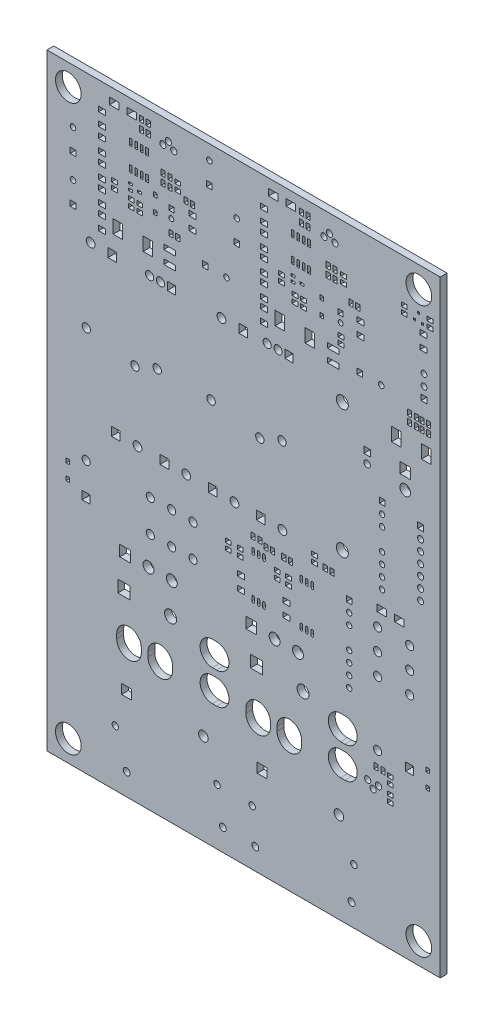
SolidWorks part; units mm, degrees
ref_plane "Plan de face" through (0, 0, 0) normal (0, 0, 1) x (1, 0, 0)
ref_plane "Plan de dessus" through (0, 0, 0) normal (0, 1, 0) x (1, 0, 0)
ref_plane "Plan de droite" through (0, 0, 0) normal (1, 0, 0) x (0, 0, -1)
sketch "Model" plane through (0, 0, 0) normal (0, 0, 1) x (1, 0, 0)
  line L0 (23.625, 30.9) -> (23.625, 31.9)
  line L1 (29.375, 31.9) -> (29.375, 30.9)
  line L2 (23.625, 30.9) -> (23.625, 31.9)
  line L3 (29.375, 31.9) -> (29.375, 30.9)
  line L4 (16.325, 30.9) -> (16.325, 31.9)
  line L5 (22.075, 31.9) -> (22.075, 30.9)
  line L6 (16.325, 30.9) -> (16.325, 31.9)
  line L7 (22.075, 31.9) -> (22.075, 30.9)
  line L8 (39.7, 36.225) -> (38.7, 36.225)
  line L9 (38.7, 41.975) -> (39.7, 41.975)
  line L10 (39.7, 36.225) -> (38.7, 36.225)
  line L11 (38.7, 41.975) -> (39.7, 41.975)
  line L12 (39.7, 28.925) -> (38.7, 28.925)
  line L13 (38.7, 34.675) -> (39.7, 34.675)
  line L14 (39.7, 28.925) -> (38.7, 28.925)
  line L15 (38.7, 34.675) -> (39.7, 34.675)
  line L16 (53.825, 30.9) -> (53.825, 31.9)
  line L17 (59.575, 31.9) -> (59.575, 30.9)
  line L18 (53.825, 30.9) -> (53.825, 31.9)
  line L19 (59.575, 31.9) -> (59.575, 30.9)
  line L20 (46.525, 30.9) -> (46.525, 31.9)
  line L21 (52.275, 31.9) -> (52.275, 30.9)
  line L22 (46.525, 30.9) -> (46.525, 31.9)
  line L23 (52.275, 31.9) -> (52.275, 30.9)
  line L24 (69.7, 36.225) -> (68.7, 36.225)
  line L25 (68.7, 41.975) -> (69.7, 41.975)
  line L26 (69.7, 36.225) -> (68.7, 36.225)
  line L27 (68.7, 41.975) -> (69.7, 41.975)
  line L28 (69.7, 28.925) -> (68.7, 28.925)
  line L29 (68.7, 34.675) -> (69.7, 34.675)
  line L30 (69.7, 28.925) -> (68.7, 28.925)
  line L31 (68.7, 34.675) -> (69.7, 34.675)
  line L32 (87.1159, 131.935) -> (86.6841, 131.935)
  line L33 (86.6841, 131.935) -> (86.6841, 132.443)
  line L34 (86.6841, 132.443) -> (87.1159, 132.443)
  line L35 (87.1159, 132.443) -> (87.1159, 131.935)
  line L36 (86.1761, 130.157) -> (85.7443, 130.157)
  line L37 (85.7443, 130.157) -> (85.7443, 130.665)
  line L38 (85.7443, 130.665) -> (86.1761, 130.665)
  line L39 (86.1761, 130.665) -> (86.1761, 130.157)
  line L40 (88.0811, 130.157) -> (87.6493, 130.157)
  line L41 (87.6493, 130.157) -> (87.6493, 130.665)
  line L42 (87.6493, 130.665) -> (88.0811, 130.665)
  line L43 (88.0811, 130.665) -> (88.0811, 130.157)
  line L44 (77.25, 66.825) -> (77.25, 68.375)
  line L45 (77.25, 68.375) -> (79.45, 68.375)
  line L46 (79.45, 68.375) -> (79.45, 66.825)
  line L47 (79.45, 66.825) -> (77.25, 66.825)
  line L48 (81.35, 66.825) -> (81.35, 68.375)
  line L49 (81.35, 68.375) -> (83.55, 68.375)
  line L50 (83.55, 68.375) -> (83.55, 66.825)
  line L51 (83.55, 66.825) -> (81.35, 66.825)
  line L52 (58.15, 139.875) -> (58.15, 138.325)
  line L53 (58.15, 138.325) -> (55.95, 138.325)
  line L54 (55.95, 138.325) -> (55.95, 139.875)
  line L55 (55.95, 139.875) -> (58.15, 139.875)
  line L56 (54.05, 139.875) -> (54.05, 138.325)
  line L57 (54.05, 138.325) -> (51.85, 138.325)
  line L58 (51.85, 138.325) -> (51.85, 139.875)
  line L59 (51.85, 139.875) -> (54.05, 139.875)
  line L60 (20.95, 139.775) -> (20.95, 138.225)
  line L61 (20.95, 138.225) -> (18.75, 138.225)
  line L62 (18.75, 138.225) -> (18.75, 139.775)
  line L63 (18.75, 139.775) -> (20.95, 139.775)
  line L64 (16.85, 139.775) -> (16.85, 138.225)
  line L65 (16.85, 138.225) -> (14.65, 138.225)
  line L66 (14.65, 138.225) -> (14.65, 139.775)
  line L67 (14.65, 139.775) -> (16.85, 139.775)
  line L68 (44.875, 109.125) -> (46.925, 109.125)
  line L69 (46.925, 109.125) -> (46.925, 107.075)
  line L70 (46.925, 107.075) -> (44.875, 107.075)
  line L71 (44.875, 107.075) -> (44.875, 109.125)
  line L72 (44.875, 109.125) -> (46.925, 109.125)
  line L73 (46.925, 109.125) -> (46.925, 107.075)
  line L74 (46.925, 107.075) -> (44.875, 107.075)
  line L75 (44.875, 107.075) -> (44.875, 109.125)
  line L76 (14.275, 109.125) -> (16.325, 109.125)
  line L77 (16.325, 109.125) -> (16.325, 107.075)
  line L78 (16.325, 107.075) -> (14.275, 107.075)
  line L79 (14.275, 107.075) -> (14.275, 109.125)
  line L80 (14.275, 109.125) -> (16.325, 109.125)
  line L81 (16.325, 109.125) -> (16.325, 107.075)
  line L82 (16.325, 107.075) -> (14.275, 107.075)
  line L83 (14.275, 107.075) -> (14.275, 109.125)
  line L84 (87.6, 106.075) -> (89.8, 106.075)
  line L85 (89.8, 106.075) -> (89.8, 102.925)
  line L86 (89.8, 102.925) -> (87.6, 102.925)
  line L87 (87.6, 102.925) -> (87.6, 106.075)
  line L88 (80.6, 106.075) -> (82.8, 106.075)
  line L89 (82.8, 106.075) -> (82.8, 102.925)
  line L90 (82.8, 102.925) -> (80.6, 102.925)
  line L91 (80.6, 102.925) -> (80.6, 106.075)
  line L92 (55.6, 112.825) -> (53.4, 112.825)
  line L93 (53.4, 112.825) -> (53.4, 115.975)
  line L94 (53.4, 115.975) -> (55.6, 115.975)
  line L95 (55.6, 115.975) -> (55.6, 112.825)
  line L96 (62.6, 112.825) -> (60.4, 112.825)
  line L97 (60.4, 112.825) -> (60.4, 115.975)
  line L98 (60.4, 115.975) -> (62.6, 115.975)
  line L99 (62.6, 115.975) -> (62.6, 112.825)
  line L100 (17.7, 112.425) -> (15.5, 112.425)
  line L101 (15.5, 112.425) -> (15.5, 115.575)
  line L102 (15.5, 115.575) -> (17.7, 115.575)
  line L103 (17.7, 115.575) -> (17.7, 112.425)
  line L104 (24.7, 112.425) -> (22.5, 112.425)
  line L105 (22.5, 112.425) -> (22.5, 115.575)
  line L106 (22.5, 115.575) -> (24.7, 115.575)
  line L107 (24.7, 115.575) -> (24.7, 112.425)
  line L108 (49.175, 20.075) -> (49.175, 22.325)
  line L109 (49.175, 22.325) -> (51.425, 22.325)
  line L110 (51.425, 22.325) -> (51.425, 20.075)
  line L111 (51.425, 20.075) -> (49.175, 20.075)
  line L112 (49.175, 20.075) -> (49.175, 22.325)
  line L113 (49.175, 22.325) -> (51.425, 22.325)
  line L114 (51.425, 22.325) -> (51.425, 20.075)
  line L115 (51.425, 20.075) -> (49.175, 20.075)
  line L116 (17.475, 20.175) -> (17.475, 22.425)
  line L117 (17.475, 22.425) -> (19.725, 22.425)
  line L118 (19.725, 22.425) -> (19.725, 20.175)
  line L119 (19.725, 20.175) -> (17.475, 20.175)
  line L120 (17.475, 20.175) -> (17.475, 22.425)
  line L121 (17.475, 22.425) -> (19.725, 22.425)
  line L122 (19.725, 22.425) -> (19.725, 20.175)
  line L123 (19.725, 20.175) -> (17.475, 20.175)
  line L124 (61.005, 134.275) -> (61.605, 134.275)
  line L125 (61.605, 134.275) -> (61.605, 132.725)
  line L126 (61.605, 132.725) -> (61.005, 132.725)
  line L127 (61.005, 132.725) -> (61.005, 134.275)
  line L128 (59.735, 134.275) -> (60.335, 134.275)
  line L129 (60.335, 134.275) -> (60.335, 132.725)
  line L130 (60.335, 132.725) -> (59.735, 132.725)
  line L131 (59.735, 132.725) -> (59.735, 134.275)
  line L132 (58.465, 134.275) -> (59.065, 134.275)
  line L133 (59.065, 134.275) -> (59.065, 132.725)
  line L134 (59.065, 132.725) -> (58.465, 132.725)
  line L135 (58.465, 132.725) -> (58.465, 134.275)
  line L136 (57.195, 134.275) -> (57.795, 134.275)
  line L137 (57.795, 134.275) -> (57.795, 132.725)
  line L138 (57.795, 132.725) -> (57.195, 132.725)
  line L139 (57.195, 132.725) -> (57.195, 134.275)
  line L140 (57.195, 128.875) -> (57.795, 128.875)
  line L141 (57.795, 128.875) -> (57.795, 127.325)
  line L142 (57.795, 127.325) -> (57.195, 127.325)
  line L143 (57.195, 127.325) -> (57.195, 128.875)
  line L144 (58.465, 128.875) -> (59.065, 128.875)
  line L145 (59.065, 128.875) -> (59.065, 127.325)
  line L146 (59.065, 127.325) -> (58.465, 127.325)
  line L147 (58.465, 127.325) -> (58.465, 128.875)
  line L148 (59.735, 128.875) -> (60.335, 128.875)
  line L149 (60.335, 128.875) -> (60.335, 127.325)
  line L150 (60.335, 127.325) -> (59.735, 127.325)
  line L151 (59.735, 127.325) -> (59.735, 128.875)
  line L152 (61.005, 128.875) -> (61.605, 128.875)
  line L153 (61.605, 128.875) -> (61.605, 127.325)
  line L154 (61.605, 127.325) -> (61.005, 127.325)
  line L155 (61.005, 127.325) -> (61.005, 128.875)
  line L156 (23.105, 133.875) -> (23.705, 133.875)
  line L157 (23.705, 133.875) -> (23.705, 132.325)
  line L158 (23.705, 132.325) -> (23.105, 132.325)
  line L159 (23.105, 132.325) -> (23.105, 133.875)
  line L160 (21.835, 133.875) -> (22.435, 133.875)
  line L161 (22.435, 133.875) -> (22.435, 132.325)
  line L162 (22.435, 132.325) -> (21.835, 132.325)
  line L163 (21.835, 132.325) -> (21.835, 133.875)
  line L164 (20.565, 133.875) -> (21.165, 133.875)
  line L165 (21.165, 133.875) -> (21.165, 132.325)
  line L166 (21.165, 132.325) -> (20.565, 132.325)
  line L167 (20.565, 132.325) -> (20.565, 133.875)
  line L168 (19.295, 133.875) -> (19.895, 133.875)
  line L169 (19.895, 133.875) -> (19.895, 132.325)
  line L170 (19.895, 132.325) -> (19.295, 132.325)
  line L171 (19.295, 132.325) -> (19.295, 133.875)
  line L172 (19.295, 128.475) -> (19.895, 128.475)
  line L173 (19.895, 128.475) -> (19.895, 126.925)
  line L174 (19.895, 126.925) -> (19.295, 126.925)
  line L175 (19.295, 126.925) -> (19.295, 128.475)
  line L176 (20.565, 128.475) -> (21.165, 128.475)
  line L177 (21.165, 128.475) -> (21.165, 126.925)
  line L178 (21.165, 126.925) -> (20.565, 126.925)
  line L179 (20.565, 126.925) -> (20.565, 128.475)
  line L180 (21.835, 128.475) -> (22.435, 128.475)
  line L181 (22.435, 128.475) -> (22.435, 126.925)
  line L182 (22.435, 126.925) -> (21.835, 126.925)
  line L183 (21.835, 126.925) -> (21.835, 128.475)
  line L184 (23.105, 128.475) -> (23.705, 128.475)
  line L185 (23.705, 128.475) -> (23.705, 126.925)
  line L186 (23.705, 126.925) -> (23.105, 126.925)
  line L187 (23.105, 126.925) -> (23.105, 128.475)
  line L188 (88.875, 114.725) -> (87.525, 114.725)
  line L189 (87.525, 114.725) -> (87.525, 116.075)
  line L190 (87.525, 116.075) -> (88.875, 116.075)
  line L191 (88.875, 116.075) -> (88.875, 114.725)
  line L192 (88.875, 114.725) -> (87.525, 114.725)
  line L193 (87.525, 114.725) -> (87.525, 116.075)
  line L194 (87.525, 116.075) -> (88.875, 116.075)
  line L195 (88.875, 116.075) -> (88.875, 114.725)
  line L196 (85.925, 109.575) -> (86.875, 109.575)
  line L197 (86.875, 109.575) -> (86.875, 108.225)
  line L198 (86.875, 108.225) -> (85.925, 108.225)
  line L199 (85.925, 108.225) -> (85.925, 109.575)
  line L200 (84.325, 109.575) -> (85.275, 109.575)
  line L201 (85.275, 109.575) -> (85.275, 108.225)
  line L202 (85.275, 108.225) -> (84.325, 108.225)
  line L203 (84.325, 108.225) -> (84.325, 109.575)
  line L204 (85.925, 111.475) -> (86.875, 111.475)
  line L205 (86.875, 111.475) -> (86.875, 110.125)
  line L206 (86.875, 110.125) -> (85.925, 110.125)
  line L207 (85.925, 110.125) -> (85.925, 111.475)
  line L208 (84.325, 111.475) -> (85.275, 111.475)
  line L209 (85.275, 111.475) -> (85.275, 110.125)
  line L210 (85.275, 110.125) -> (84.325, 110.125)
  line L211 (84.325, 110.125) -> (84.325, 111.475)
  line L212 (74.15, 98.85) -> (75.65, 98.85)
  line L213 (75.65, 98.85) -> (75.65, 97.35)
  line L214 (75.65, 97.35) -> (74.15, 97.35)
  line L215 (74.15, 97.35) -> (74.15, 98.85)
  line L216 (74.15, 98.85) -> (75.65, 98.85)
  line L217 (75.65, 98.85) -> (75.65, 97.35)
  line L218 (75.65, 97.35) -> (74.15, 97.35)
  line L219 (74.15, 97.35) -> (74.15, 98.85)
  line L220 (86.7, 89.8) -> (88.1, 89.8)
  line L221 (88.1, 89.8) -> (88.1, 88.4)
  line L222 (88.1, 88.4) -> (86.7, 88.4)
  line L223 (86.7, 88.4) -> (86.7, 89.8)
  line L224 (86.7, 89.8) -> (88.1, 89.8)
  line L225 (88.1, 89.8) -> (88.1, 88.4)
  line L226 (88.1, 88.4) -> (86.7, 88.4)
  line L227 (86.7, 88.4) -> (86.7, 89.8)
  line L228 (82.55, 99.95) -> (85.05, 99.95)
  line L229 (85.05, 99.95) -> (85.05, 97.45)
  line L230 (85.05, 97.45) -> (82.55, 97.45)
  line L231 (82.55, 97.45) -> (82.55, 99.95)
  line L232 (82.55, 99.95) -> (85.05, 99.95)
  line L233 (85.05, 99.95) -> (85.05, 97.45)
  line L234 (85.05, 97.45) -> (82.55, 97.45)
  line L235 (82.55, 97.45) -> (82.55, 99.95)
  line L236 (70.075, 65.275) -> (70.075, 66.525)
  line L237 (70.075, 66.525) -> (71.325, 66.525)
  line L238 (71.325, 66.525) -> (71.325, 65.275)
  line L239 (71.325, 65.275) -> (70.075, 65.275)
  line L240 (70.075, 65.275) -> (70.075, 66.525)
  line L241 (70.075, 66.525) -> (71.325, 66.525)
  line L242 (71.325, 66.525) -> (71.325, 65.275)
  line L243 (71.325, 65.275) -> (70.075, 65.275)
  line L244 (77.775, 89.075) -> (77.775, 90.325)
  line L245 (77.775, 90.325) -> (79.025, 90.325)
  line L246 (79.025, 90.325) -> (79.025, 89.075)
  line L247 (79.025, 89.075) -> (77.775, 89.075)
  line L248 (77.775, 89.075) -> (77.775, 90.325)
  line L249 (77.775, 90.325) -> (79.025, 90.325)
  line L250 (79.025, 90.325) -> (79.025, 89.075)
  line L251 (79.025, 89.075) -> (77.775, 89.075)
  line L252 (61.77, 64.075) -> (61.77, 65.025)
  line L253 (62.37, 65.025) -> (62.37, 64.075)
  line L254 (60.5, 64.075) -> (60.5, 65.025)
  line L255 (61.1, 65.025) -> (61.1, 64.075)
  line L256 (59.23, 64.075) -> (59.23, 65.025)
  line L257 (59.83, 65.025) -> (59.83, 64.075)
  line L258 (59.23, 54.375) -> (59.23, 55.325)
  line L259 (59.83, 55.325) -> (59.83, 54.375)
  line L260 (60.5, 54.375) -> (60.5, 55.325)
  line L261 (61.1, 55.325) -> (61.1, 54.375)
  line L262 (61.77, 54.375) -> (61.77, 55.325)
  line L263 (62.37, 55.325) -> (62.37, 54.375)
  line L264 (50.47, 64.075) -> (50.47, 65.025)
  line L265 (51.07, 65.025) -> (51.07, 64.075)
  line L266 (49.2, 64.075) -> (49.2, 65.025)
  line L267 (49.8, 65.025) -> (49.8, 64.075)
  line L268 (47.93, 64.075) -> (47.93, 65.025)
  line L269 (48.53, 65.025) -> (48.53, 64.075)
  line L270 (47.93, 54.375) -> (47.93, 55.325)
  line L271 (48.53, 55.325) -> (48.53, 54.375)
  line L272 (49.2, 54.375) -> (49.2, 55.325)
  line L273 (49.8, 55.325) -> (49.8, 54.375)
  line L274 (50.47, 54.375) -> (50.47, 55.325)
  line L275 (51.07, 55.325) -> (51.07, 54.375)
  line L276 (50.4, 40.6) -> (47.6, 40.6)
  line L277 (47.6, 40.6) -> (47.6, 43.4)
  line L278 (47.6, 43.4) -> (50.4, 43.4)
  line L279 (50.4, 43.4) -> (50.4, 40.6)
  line L280 (50.4, 40.6) -> (47.6, 40.6)
  line L281 (47.6, 40.6) -> (47.6, 43.4)
  line L282 (47.6, 43.4) -> (50.4, 43.4)
  line L283 (50.4, 43.4) -> (50.4, 40.6)
  line L284 (19.4, 40.3) -> (16.6, 40.3)
  line L285 (16.6, 40.3) -> (16.6, 43.1)
  line L286 (16.6, 43.1) -> (19.4, 43.1)
  line L287 (19.4, 43.1) -> (19.4, 40.3)
  line L288 (19.4, 40.3) -> (16.6, 40.3)
  line L289 (16.6, 40.3) -> (16.6, 43.1)
  line L290 (16.6, 43.1) -> (19.4, 43.1)
  line L291 (19.4, 43.1) -> (19.4, 40.3)
  line L292 (49.075, 48.025) -> (46.525, 48.025)
  line L293 (46.525, 48.025) -> (46.525, 50.575)
  line L294 (46.525, 50.575) -> (49.075, 50.575)
  line L295 (49.075, 50.575) -> (49.075, 48.025)
  line L296 (49.075, 48.025) -> (46.525, 48.025)
  line L297 (46.525, 48.025) -> (46.525, 50.575)
  line L298 (46.525, 50.575) -> (49.075, 50.575)
  line L299 (49.075, 50.575) -> (49.075, 48.025)
  line L300 (19.575, 47.825) -> (17.025, 47.825)
  line L301 (17.025, 47.825) -> (17.025, 50.375)
  line L302 (17.025, 50.375) -> (19.575, 50.375)
  line L303 (19.575, 50.375) -> (19.575, 47.825)
  line L304 (19.575, 47.825) -> (17.025, 47.825)
  line L305 (17.025, 47.825) -> (17.025, 50.375)
  line L306 (17.025, 50.375) -> (19.575, 50.375)
  line L307 (19.575, 50.375) -> (19.575, 47.825)
  line L308 (38.65, 132.95) -> (37.35, 132.95)
  line L309 (37.35, 132.95) -> (37.35, 134.25)
  line L310 (37.35, 134.25) -> (38.65, 134.25)
  line L311 (38.65, 134.25) -> (38.65, 132.95)
  line L312 (38.65, 132.95) -> (37.35, 132.95)
  line L313 (37.35, 132.95) -> (37.35, 134.25)
  line L314 (37.35, 134.25) -> (38.65, 134.25)
  line L315 (38.65, 134.25) -> (38.65, 132.95)
  line L316 (45.05, 124.45) -> (43.75, 124.45)
  line L317 (43.75, 124.45) -> (43.75, 125.75)
  line L318 (43.75, 125.75) -> (45.05, 125.75)
  line L319 (45.05, 125.75) -> (45.05, 124.45)
  line L320 (45.05, 124.45) -> (43.75, 124.45)
  line L321 (43.75, 124.45) -> (43.75, 125.75)
  line L322 (43.75, 125.75) -> (45.05, 125.75)
  line L323 (45.05, 125.75) -> (45.05, 124.45)
  line L324 (6.75, 123.75) -> (5.45, 123.75)
  line L325 (5.45, 123.75) -> (5.45, 125.05)
  line L326 (5.45, 125.05) -> (6.75, 125.05)
  line L327 (6.75, 125.05) -> (6.75, 123.75)
  line L328 (6.75, 123.75) -> (5.45, 123.75)
  line L329 (5.45, 123.75) -> (5.45, 125.05)
  line L330 (5.45, 125.05) -> (6.75, 125.05)
  line L331 (6.75, 125.05) -> (6.75, 123.75)
  line L332 (6.75, 113.05) -> (5.45, 113.05)
  line L333 (5.45, 113.05) -> (5.45, 114.35)
  line L334 (5.45, 114.35) -> (6.75, 114.35)
  line L335 (6.75, 114.35) -> (6.75, 113.05)
  line L336 (6.75, 113.05) -> (5.45, 113.05)
  line L337 (5.45, 113.05) -> (5.45, 114.35)
  line L338 (5.45, 114.35) -> (6.75, 114.35)
  line L339 (6.75, 114.35) -> (6.75, 113.05)
  line L340 (88.925, 126.075) -> (88.925, 124.925)
  line L341 (88.925, 124.925) -> (87.275, 124.925)
  line L342 (87.275, 124.925) -> (87.275, 126.075)
  line L343 (87.275, 126.075) -> (88.925, 126.075)
  line L344 (88.925, 129.075) -> (88.925, 127.925)
  line L345 (88.925, 127.925) -> (87.275, 127.925)
  line L346 (87.275, 127.925) -> (87.275, 129.075)
  line L347 (87.275, 129.075) -> (88.925, 129.075)
  line L348 (56.825, 55.775) -> (56.825, 54.625)
  line L349 (56.825, 54.625) -> (55.175, 54.625)
  line L350 (55.175, 54.625) -> (55.175, 55.775)
  line L351 (55.175, 55.775) -> (56.825, 55.775)
  line L352 (56.825, 58.775) -> (56.825, 57.625)
  line L353 (56.825, 57.625) -> (55.175, 57.625)
  line L354 (55.175, 57.625) -> (55.175, 58.775)
  line L355 (55.175, 58.775) -> (56.825, 58.775)
  line L356 (46.225, 55.875) -> (46.225, 54.725)
  line L357 (46.225, 54.725) -> (44.575, 54.725)
  line L358 (44.575, 54.725) -> (44.575, 55.875)
  line L359 (44.575, 55.875) -> (46.225, 55.875)
  line L360 (46.225, 58.875) -> (46.225, 57.725)
  line L361 (46.225, 57.725) -> (44.575, 57.725)
  line L362 (44.575, 57.725) -> (44.575, 58.875)
  line L363 (44.575, 58.875) -> (46.225, 58.875)
  line L364 (74.225, 121.275) -> (74.225, 120.125)
  line L365 (74.225, 120.125) -> (72.575, 120.125)
  line L366 (72.575, 120.125) -> (72.575, 121.275)
  line L367 (72.575, 121.275) -> (74.225, 121.275)
  line L368 (74.225, 124.275) -> (74.225, 123.125)
  line L369 (74.225, 123.125) -> (72.575, 123.125)
  line L370 (72.575, 123.125) -> (72.575, 124.275)
  line L371 (72.575, 124.275) -> (74.225, 124.275)
  line L372 (34.925, 123.175) -> (34.925, 122.025)
  line L373 (34.925, 122.025) -> (33.275, 122.025)
  line L374 (33.275, 122.025) -> (33.275, 123.175)
  line L375 (33.275, 123.175) -> (34.925, 123.175)
  line L376 (34.925, 126.175) -> (34.925, 125.025)
  line L377 (34.925, 125.025) -> (33.275, 125.025)
  line L378 (33.275, 125.025) -> (33.275, 126.175)
  line L379 (33.275, 126.175) -> (34.925, 126.175)
  line L380 (49.975, 134.825) -> (49.975, 135.975)
  line L381 (49.975, 135.975) -> (51.625, 135.975)
  line L382 (51.625, 135.975) -> (51.625, 134.825)
  line L383 (51.625, 134.825) -> (49.975, 134.825)
  line L384 (49.975, 131.825) -> (49.975, 132.975)
  line L385 (49.975, 132.975) -> (51.625, 132.975)
  line L386 (51.625, 132.975) -> (51.625, 131.825)
  line L387 (51.625, 131.825) -> (49.975, 131.825)
  line L388 (12.075, 135.525) -> (12.075, 136.675)
  line L389 (12.075, 136.675) -> (13.725, 136.675)
  line L390 (13.725, 136.675) -> (13.725, 135.525)
  line L391 (13.725, 135.525) -> (12.075, 135.525)
  line L392 (12.075, 132.525) -> (12.075, 133.675)
  line L393 (12.075, 133.675) -> (13.725, 133.675)
  line L394 (13.725, 133.675) -> (13.725, 132.525)
  line L395 (13.725, 132.525) -> (12.075, 132.525)
  line L396 (51.625, 127.775) -> (51.625, 126.625)
  line L397 (51.625, 126.625) -> (49.975, 126.625)
  line L398 (49.975, 126.625) -> (49.975, 127.775)
  line L399 (49.975, 127.775) -> (51.625, 127.775)
  line L400 (51.625, 130.775) -> (51.625, 129.625)
  line L401 (51.625, 129.625) -> (49.975, 129.625)
  line L402 (49.975, 129.625) -> (49.975, 130.775)
  line L403 (49.975, 130.775) -> (51.625, 130.775)
  line L404 (51.625, 122.775) -> (51.625, 121.625)
  line L405 (51.625, 121.625) -> (49.975, 121.625)
  line L406 (49.975, 121.625) -> (49.975, 122.775)
  line L407 (49.975, 122.775) -> (51.625, 122.775)
  line L408 (51.625, 125.775) -> (51.625, 124.625)
  line L409 (51.625, 124.625) -> (49.975, 124.625)
  line L410 (49.975, 124.625) -> (49.975, 125.775)
  line L411 (49.975, 125.775) -> (51.625, 125.775)
  line L412 (51.625, 112.675) -> (51.625, 111.525)
  line L413 (51.625, 111.525) -> (49.975, 111.525)
  line L414 (49.975, 111.525) -> (49.975, 112.675)
  line L415 (49.975, 112.675) -> (51.625, 112.675)
  line L416 (51.625, 115.675) -> (51.625, 114.525)
  line L417 (51.625, 114.525) -> (49.975, 114.525)
  line L418 (49.975, 114.525) -> (49.975, 115.675)
  line L419 (49.975, 115.675) -> (51.625, 115.675)
  line L420 (51.625, 117.675) -> (51.625, 116.525)
  line L421 (51.625, 116.525) -> (49.975, 116.525)
  line L422 (49.975, 116.525) -> (49.975, 117.675)
  line L423 (49.975, 117.675) -> (51.625, 117.675)
  line L424 (51.625, 120.675) -> (51.625, 119.525)
  line L425 (51.625, 119.525) -> (49.975, 119.525)
  line L426 (49.975, 119.525) -> (49.975, 120.675)
  line L427 (49.975, 120.675) -> (51.625, 120.675)
  line L428 (13.725, 128.275) -> (13.725, 127.125)
  line L429 (13.725, 127.125) -> (12.075, 127.125)
  line L430 (12.075, 127.125) -> (12.075, 128.275)
  line L431 (12.075, 128.275) -> (13.725, 128.275)
  line L432 (13.725, 131.275) -> (13.725, 130.125)
  line L433 (13.725, 130.125) -> (12.075, 130.125)
  line L434 (12.075, 130.125) -> (12.075, 131.275)
  line L435 (12.075, 131.275) -> (13.725, 131.275)
  line L436 (13.725, 122.975) -> (13.725, 121.825)
  line L437 (13.725, 121.825) -> (12.075, 121.825)
  line L438 (12.075, 121.825) -> (12.075, 122.975)
  line L439 (12.075, 122.975) -> (13.725, 122.975)
  line L440 (13.725, 125.975) -> (13.725, 124.825)
  line L441 (13.725, 124.825) -> (12.075, 124.825)
  line L442 (12.075, 124.825) -> (12.075, 125.975)
  line L443 (12.075, 125.975) -> (13.725, 125.975)
  line L444 (13.725, 117.775) -> (13.725, 116.625)
  line L445 (13.725, 116.625) -> (12.075, 116.625)
  line L446 (12.075, 116.625) -> (12.075, 117.775)
  line L447 (12.075, 117.775) -> (13.725, 117.775)
  line L448 (13.725, 120.775) -> (13.725, 119.625)
  line L449 (13.725, 119.625) -> (12.075, 119.625)
  line L450 (12.075, 119.625) -> (12.075, 120.775)
  line L451 (12.075, 120.775) -> (13.725, 120.775)
  line L452 (13.725, 112.575) -> (13.725, 111.425)
  line L453 (13.725, 111.425) -> (12.075, 111.425)
  line L454 (12.075, 111.425) -> (12.075, 112.575)
  line L455 (12.075, 112.575) -> (13.725, 112.575)
  line L456 (13.725, 115.575) -> (13.725, 114.425)
  line L457 (13.725, 114.425) -> (12.075, 114.425)
  line L458 (12.075, 114.425) -> (12.075, 115.575)
  line L459 (12.075, 115.575) -> (13.725, 115.575)
  line L460 (72.55, 112.55) -> (72.55, 113.85)
  line L461 (72.55, 113.85) -> (73.85, 113.85)
  line L462 (73.85, 113.85) -> (73.85, 112.55)
  line L463 (73.85, 112.55) -> (72.55, 112.55)
  line L464 (72.55, 112.55) -> (72.55, 113.85)
  line L465 (72.55, 113.85) -> (73.85, 113.85)
  line L466 (73.85, 113.85) -> (73.85, 112.55)
  line L467 (73.85, 112.55) -> (72.55, 112.55)
  line L468 (36.35, 116.25) -> (36.35, 117.55)
  line L469 (36.35, 117.55) -> (37.65, 117.55)
  line L470 (37.65, 117.55) -> (37.65, 116.25)
  line L471 (37.65, 116.25) -> (36.35, 116.25)
  line L472 (36.35, 116.25) -> (36.35, 117.55)
  line L473 (36.35, 117.55) -> (37.65, 117.55)
  line L474 (37.65, 117.55) -> (37.65, 116.25)
  line L475 (37.65, 116.25) -> (36.35, 116.25)
  line L476 (68.125, 123.675) -> (69.275, 123.675)
  line L477 (69.275, 123.675) -> (69.275, 122.525)
  line L478 (69.275, 122.525) -> (68.125, 122.525)
  line L479 (68.125, 122.525) -> (68.125, 123.675)
  line L480 (68.125, 123.675) -> (69.275, 123.675)
  line L481 (69.275, 123.675) -> (69.275, 122.525)
  line L482 (69.275, 122.525) -> (68.125, 122.525)
  line L483 (68.125, 122.525) -> (68.125, 123.675)
  line L484 (28.525, 124.975) -> (29.675, 124.975)
  line L485 (29.675, 124.975) -> (29.675, 123.825)
  line L486 (29.675, 123.825) -> (28.525, 123.825)
  line L487 (28.525, 123.825) -> (28.525, 124.975)
  line L488 (28.525, 124.975) -> (29.675, 124.975)
  line L489 (29.675, 124.975) -> (29.675, 123.825)
  line L490 (29.675, 123.825) -> (28.525, 123.825)
  line L491 (28.525, 123.825) -> (28.525, 124.975)
  line L492 (68.35, 112.575) -> (68.35, 111.425)
  line L493 (68.35, 111.425) -> (65.65, 111.425)
  line L494 (65.65, 111.425) -> (65.65, 112.575)
  line L495 (65.65, 112.575) -> (68.35, 112.575)
  line L496 (68.35, 115.575) -> (68.35, 114.425)
  line L497 (68.35, 114.425) -> (65.65, 114.425)
  line L498 (65.65, 114.425) -> (65.65, 115.575)
  line L499 (65.65, 115.575) -> (68.35, 115.575)
  line L500 (30.05, 113.375) -> (30.05, 112.225)
  line L501 (30.05, 112.225) -> (27.35, 112.225)
  line L502 (27.35, 112.225) -> (27.35, 113.375)
  line L503 (27.35, 113.375) -> (30.05, 113.375)
  line L504 (30.05, 116.375) -> (30.05, 115.225)
  line L505 (30.05, 115.225) -> (27.35, 115.225)
  line L506 (27.35, 115.225) -> (27.35, 116.375)
  line L507 (27.35, 116.375) -> (30.05, 116.375)
  line L508 (88.925, 131.625) -> (88.925, 132.575)
  line L509 (88.925, 132.575) -> (90.275, 132.575)
  line L510 (90.275, 132.575) -> (90.275, 131.625)
  line L511 (90.275, 131.625) -> (88.925, 131.625)
  line L512 (88.925, 130.025) -> (88.925, 130.975)
  line L513 (88.925, 130.975) -> (90.275, 130.975)
  line L514 (90.275, 130.975) -> (90.275, 130.025)
  line L515 (90.275, 130.025) -> (88.925, 130.025)
  line L516 (84.275, 130.875) -> (84.275, 129.925)
  line L517 (84.275, 129.925) -> (82.925, 129.925)
  line L518 (82.925, 129.925) -> (82.925, 130.875)
  line L519 (82.925, 130.875) -> (84.275, 130.875)
  line L520 (84.275, 132.475) -> (84.275, 131.525)
  line L521 (84.275, 131.525) -> (82.925, 131.525)
  line L522 (82.925, 131.525) -> (82.925, 132.475)
  line L523 (82.925, 132.475) -> (84.275, 132.475)
  line L524 (88.175, 108.225) -> (87.225, 108.225)
  line L525 (87.225, 108.225) -> (87.225, 109.575)
  line L526 (87.225, 109.575) -> (88.175, 109.575)
  line L527 (88.175, 109.575) -> (88.175, 108.225)
  line L528 (89.775, 108.225) -> (88.825, 108.225)
  line L529 (88.825, 108.225) -> (88.825, 109.575)
  line L530 (88.825, 109.575) -> (89.775, 109.575)
  line L531 (89.775, 109.575) -> (89.775, 108.225)
  line L532 (77.475, 34.625) -> (76.525, 34.625)
  line L533 (76.525, 34.625) -> (76.525, 35.975)
  line L534 (76.525, 35.975) -> (77.475, 35.975)
  line L535 (77.475, 35.975) -> (77.475, 34.625)
  line L536 (79.075, 34.625) -> (78.125, 34.625)
  line L537 (78.125, 34.625) -> (78.125, 35.975)
  line L538 (78.125, 35.975) -> (79.075, 35.975)
  line L539 (79.075, 35.975) -> (79.075, 34.625)
  line L540 (55.875, 66.225) -> (54.925, 66.225)
  line L541 (54.925, 66.225) -> (54.925, 67.575)
  line L542 (54.925, 67.575) -> (55.875, 67.575)
  line L543 (55.875, 67.575) -> (55.875, 66.225)
  line L544 (57.475, 66.225) -> (56.525, 66.225)
  line L545 (56.525, 66.225) -> (56.525, 67.575)
  line L546 (56.525, 67.575) -> (57.475, 67.575)
  line L547 (57.475, 67.575) -> (57.475, 66.225)
  line L548 (48.675, 66.925) -> (47.725, 66.925)
  line L549 (47.725, 66.925) -> (47.725, 68.275)
  line L550 (47.725, 68.275) -> (48.675, 68.275)
  line L551 (48.675, 68.275) -> (48.675, 66.925)
  line L552 (50.275, 66.925) -> (49.325, 66.925)
  line L553 (49.325, 66.925) -> (49.325, 68.275)
  line L554 (49.325, 68.275) -> (50.275, 68.275)
  line L555 (50.275, 68.275) -> (50.275, 66.925)
  line L556 (65.575, 68.925) -> (64.625, 68.925)
  line L557 (64.625, 68.925) -> (64.625, 70.275)
  line L558 (64.625, 70.275) -> (65.575, 70.275)
  line L559 (65.575, 70.275) -> (65.575, 68.925)
  line L560 (67.175, 68.925) -> (66.225, 68.925)
  line L561 (66.225, 68.925) -> (66.225, 70.275)
  line L562 (66.225, 70.275) -> (67.175, 70.275)
  line L563 (67.175, 70.275) -> (67.175, 68.925)
  line L564 (52.325, 67.575) -> (53.275, 67.575)
  line L565 (53.275, 67.575) -> (53.275, 66.225)
  line L566 (53.275, 66.225) -> (52.325, 66.225)
  line L567 (52.325, 66.225) -> (52.325, 67.575)
  line L568 (50.725, 67.575) -> (51.675, 67.575)
  line L569 (51.675, 67.575) -> (51.675, 66.225)
  line L570 (51.675, 66.225) -> (50.725, 66.225)
  line L571 (50.725, 66.225) -> (50.725, 67.575)
  line L572 (88.175, 110.125) -> (87.225, 110.125)
  line L573 (87.225, 110.125) -> (87.225, 111.475)
  line L574 (87.225, 111.475) -> (88.175, 111.475)
  line L575 (88.175, 111.475) -> (88.175, 110.125)
  line L576 (89.775, 110.125) -> (88.825, 110.125)
  line L577 (88.825, 110.125) -> (88.825, 111.475)
  line L578 (88.825, 111.475) -> (89.775, 111.475)
  line L579 (89.775, 111.475) -> (89.775, 110.125)
  line L580 (80.975, 30.175) -> (80.975, 29.225)
  line L581 (80.975, 29.225) -> (79.625, 29.225)
  line L582 (79.625, 29.225) -> (79.625, 30.175)
  line L583 (79.625, 30.175) -> (80.975, 30.175)
  line L584 (80.975, 31.775) -> (80.975, 30.825)
  line L585 (80.975, 30.825) -> (79.625, 30.825)
  line L586 (79.625, 30.825) -> (79.625, 31.775)
  line L587 (79.625, 31.775) -> (80.975, 31.775)
  line L588 (80.975, 33.875) -> (80.975, 32.925)
  line L589 (80.975, 32.925) -> (79.625, 32.925)
  line L590 (79.625, 32.925) -> (79.625, 33.875)
  line L591 (79.625, 33.875) -> (80.975, 33.875)
  line L592 (80.975, 35.475) -> (80.975, 34.525)
  line L593 (80.975, 34.525) -> (79.625, 34.525)
  line L594 (79.625, 34.525) -> (79.625, 35.475)
  line L595 (79.625, 35.475) -> (80.975, 35.475)
  line L596 (61.925, 70.525) -> (61.925, 71.475)
  line L597 (61.925, 71.475) -> (63.275, 71.475)
  line L598 (63.275, 71.475) -> (63.275, 70.525)
  line L599 (63.275, 70.525) -> (61.925, 70.525)
  line L600 (61.925, 68.925) -> (61.925, 69.875)
  line L601 (61.925, 69.875) -> (63.275, 69.875)
  line L602 (63.275, 69.875) -> (63.275, 68.925)
  line L603 (63.275, 68.925) -> (61.925, 68.925)
  line L604 (55.825, 62.925) -> (55.825, 63.875)
  line L605 (55.825, 63.875) -> (57.175, 63.875)
  line L606 (57.175, 63.875) -> (57.175, 62.925)
  line L607 (57.175, 62.925) -> (55.825, 62.925)
  line L608 (55.825, 61.325) -> (55.825, 62.275)
  line L609 (55.825, 62.275) -> (57.175, 62.275)
  line L610 (57.175, 62.275) -> (57.175, 61.325)
  line L611 (57.175, 61.325) -> (55.825, 61.325)
  line L612 (53.225, 62.925) -> (53.225, 63.875)
  line L613 (53.225, 63.875) -> (54.575, 63.875)
  line L614 (54.575, 63.875) -> (54.575, 62.925)
  line L615 (54.575, 62.925) -> (53.225, 62.925)
  line L616 (53.225, 61.325) -> (53.225, 62.275)
  line L617 (53.225, 62.275) -> (54.575, 62.275)
  line L618 (54.575, 62.275) -> (54.575, 61.325)
  line L619 (54.575, 61.325) -> (53.225, 61.325)
  line L620 (44.525, 63.125) -> (44.525, 64.075)
  line L621 (44.525, 64.075) -> (45.875, 64.075)
  line L622 (45.875, 64.075) -> (45.875, 63.125)
  line L623 (45.875, 63.125) -> (44.525, 63.125)
  line L624 (44.525, 61.525) -> (44.525, 62.475)
  line L625 (44.525, 62.475) -> (45.875, 62.475)
  line L626 (45.875, 62.475) -> (45.875, 61.525)
  line L627 (45.875, 61.525) -> (44.525, 61.525)
  line L628 (41.725, 63.125) -> (41.725, 64.075)
  line L629 (41.725, 64.075) -> (43.075, 64.075)
  line L630 (43.075, 64.075) -> (43.075, 63.125)
  line L631 (43.075, 63.125) -> (41.725, 63.125)
  line L632 (41.725, 61.525) -> (41.725, 62.475)
  line L633 (41.725, 62.475) -> (43.075, 62.475)
  line L634 (43.075, 62.475) -> (43.075, 61.525)
  line L635 (43.075, 61.525) -> (41.725, 61.525)
  line L636 (68.125, 117.925) -> (68.125, 118.875)
  line L637 (68.125, 118.875) -> (69.475, 118.875)
  line L638 (69.475, 118.875) -> (69.475, 117.925)
  line L639 (69.475, 117.925) -> (68.125, 117.925)
  line L640 (68.125, 116.325) -> (68.125, 117.275)
  line L641 (68.125, 117.275) -> (69.475, 117.275)
  line L642 (69.475, 117.275) -> (69.475, 116.325)
  line L643 (69.475, 116.325) -> (68.125, 116.325)
  line L644 (29.475, 118.625) -> (28.525, 118.625)
  line L645 (28.525, 118.625) -> (28.525, 119.975)
  line L646 (28.525, 119.975) -> (29.475, 119.975)
  line L647 (29.475, 119.975) -> (29.475, 118.625)
  line L648 (31.075, 118.625) -> (30.125, 118.625)
  line L649 (30.125, 118.625) -> (30.125, 119.975)
  line L650 (30.125, 119.975) -> (31.075, 119.975)
  line L651 (31.075, 119.975) -> (31.075, 118.625)
  line L652 (33.625, 128.375) -> (34.575, 128.375)
  line L653 (34.575, 128.375) -> (34.575, 127.025)
  line L654 (34.575, 127.025) -> (33.625, 127.025)
  line L655 (33.625, 127.025) -> (33.625, 128.375)
  line L656 (32.025, 128.375) -> (32.975, 128.375)
  line L657 (32.975, 128.375) -> (32.975, 127.025)
  line L658 (32.975, 127.025) -> (32.025, 127.025)
  line L659 (32.025, 127.025) -> (32.025, 128.375)
  line L660 (70.075, 129.875) -> (70.075, 128.925)
  line L661 (70.075, 128.925) -> (68.725, 128.925)
  line L662 (68.725, 128.925) -> (68.725, 129.875)
  line L663 (68.725, 129.875) -> (70.075, 129.875)
  line L664 (70.075, 131.475) -> (70.075, 130.525)
  line L665 (70.075, 130.525) -> (68.725, 130.525)
  line L666 (68.725, 130.525) -> (68.725, 131.475)
  line L667 (68.725, 131.475) -> (70.075, 131.475)
  line L668 (31.275, 129.275) -> (31.275, 128.325)
  line L669 (31.275, 128.325) -> (29.925, 128.325)
  line L670 (29.925, 128.325) -> (29.925, 129.275)
  line L671 (29.925, 129.275) -> (31.275, 129.275)
  line L672 (31.275, 130.875) -> (31.275, 129.925)
  line L673 (31.275, 129.925) -> (29.925, 129.925)
  line L674 (29.925, 129.925) -> (29.925, 130.875)
  line L675 (29.925, 130.875) -> (31.275, 130.875)
  line L676 (59.975, 136.025) -> (59.025, 136.025)
  line L677 (59.025, 136.025) -> (59.025, 137.375)
  line L678 (59.025, 137.375) -> (59.975, 137.375)
  line L679 (59.975, 137.375) -> (59.975, 136.025)
  line L680 (61.575, 136.025) -> (60.625, 136.025)
  line L681 (60.625, 136.025) -> (60.625, 137.375)
  line L682 (60.625, 137.375) -> (61.575, 137.375)
  line L683 (61.575, 137.375) -> (61.575, 136.025)
  line L684 (60.625, 139.575) -> (61.575, 139.575)
  line L685 (61.575, 139.575) -> (61.575, 138.225)
  line L686 (61.575, 138.225) -> (60.625, 138.225)
  line L687 (60.625, 138.225) -> (60.625, 139.575)
  line L688 (59.025, 139.575) -> (59.975, 139.575)
  line L689 (59.975, 139.575) -> (59.975, 138.225)
  line L690 (59.975, 138.225) -> (59.025, 138.225)
  line L691 (59.025, 138.225) -> (59.025, 139.575)
  line L692 (22.575, 136.225) -> (21.625, 136.225)
  line L693 (21.625, 136.225) -> (21.625, 137.575)
  line L694 (21.625, 137.575) -> (22.575, 137.575)
  line L695 (22.575, 137.575) -> (22.575, 136.225)
  line L696 (24.175, 136.225) -> (23.225, 136.225)
  line L697 (23.225, 136.225) -> (23.225, 137.575)
  line L698 (23.225, 137.575) -> (24.175, 137.575)
  line L699 (24.175, 137.575) -> (24.175, 136.225)
  line L700 (23.225, 139.675) -> (24.175, 139.675)
  line L701 (24.175, 139.675) -> (24.175, 138.325)
  line L702 (24.175, 138.325) -> (23.225, 138.325)
  line L703 (23.225, 138.325) -> (23.225, 139.675)
  line L704 (21.625, 139.675) -> (22.575, 139.675)
  line L705 (22.575, 139.675) -> (22.575, 138.325)
  line L706 (22.575, 138.325) -> (21.625, 138.325)
  line L707 (21.625, 138.325) -> (21.625, 139.675)
  line L708 (55.575, 122.875) -> (55.575, 121.925)
  line L709 (55.575, 121.925) -> (54.225, 121.925)
  line L710 (54.225, 121.925) -> (54.225, 122.875)
  line L711 (54.225, 122.875) -> (55.575, 122.875)
  line L712 (55.575, 124.475) -> (55.575, 123.525)
  line L713 (55.575, 123.525) -> (54.225, 123.525)
  line L714 (54.225, 123.525) -> (54.225, 124.475)
  line L715 (54.225, 124.475) -> (55.575, 124.475)
  line L716 (58.675, 120.275) -> (58.675, 119.325)
  line L717 (58.675, 119.325) -> (57.325, 119.325)
  line L718 (57.325, 119.325) -> (57.325, 120.275)
  line L719 (57.325, 120.275) -> (58.675, 120.275)
  line L720 (58.675, 121.875) -> (58.675, 120.925)
  line L721 (58.675, 120.925) -> (57.325, 120.925)
  line L722 (57.325, 120.925) -> (57.325, 121.875)
  line L723 (57.325, 121.875) -> (58.675, 121.875)
  line L724 (60.675, 120.275) -> (60.675, 119.325)
  line L725 (60.675, 119.325) -> (59.325, 119.325)
  line L726 (59.325, 119.325) -> (59.325, 120.275)
  line L727 (59.325, 120.275) -> (60.675, 120.275)
  line L728 (60.675, 121.875) -> (60.675, 120.925)
  line L729 (60.675, 120.925) -> (59.325, 120.925)
  line L730 (59.325, 120.925) -> (59.325, 121.875)
  line L731 (59.325, 121.875) -> (60.675, 121.875)
  line L732 (16.475, 122.175) -> (16.475, 121.225)
  line L733 (16.475, 121.225) -> (15.125, 121.225)
  line L734 (15.125, 121.225) -> (15.125, 122.175)
  line L735 (15.125, 122.175) -> (16.475, 122.175)
  line L736 (16.475, 123.775) -> (16.475, 122.825)
  line L737 (16.475, 122.825) -> (15.125, 122.825)
  line L738 (15.125, 122.825) -> (15.125, 123.775)
  line L739 (15.125, 123.775) -> (16.475, 123.775)
  line L740 (20.375, 120.475) -> (20.375, 119.525)
  line L741 (20.375, 119.525) -> (19.025, 119.525)
  line L742 (19.025, 119.525) -> (19.025, 120.475)
  line L743 (19.025, 120.475) -> (20.375, 120.475)
  line L744 (20.375, 122.075) -> (20.375, 121.125)
  line L745 (20.375, 121.125) -> (19.025, 121.125)
  line L746 (19.025, 121.125) -> (19.025, 122.075)
  line L747 (19.025, 122.075) -> (20.375, 122.075)
  line L748 (22.375, 120.475) -> (22.375, 119.525)
  line L749 (22.375, 119.525) -> (21.025, 119.525)
  line L750 (21.025, 119.525) -> (21.025, 120.475)
  line L751 (21.025, 120.475) -> (22.375, 120.475)
  line L752 (22.375, 122.075) -> (22.375, 121.125)
  line L753 (22.375, 121.125) -> (21.025, 121.125)
  line L754 (21.025, 121.125) -> (21.025, 122.075)
  line L755 (21.025, 122.075) -> (22.375, 122.075)
  line L756 (66.275, 130.525) -> (65.325, 130.525)
  line L757 (65.325, 130.525) -> (65.325, 131.875)
  line L758 (65.325, 131.875) -> (66.275, 131.875)
  line L759 (66.275, 131.875) -> (66.275, 130.525)
  line L760 (67.875, 130.525) -> (66.925, 130.525)
  line L761 (66.925, 130.525) -> (66.925, 131.875)
  line L762 (66.925, 131.875) -> (67.875, 131.875)
  line L763 (67.875, 131.875) -> (67.875, 130.525)
  line L764 (66.925, 129.875) -> (67.875, 129.875)
  line L765 (67.875, 129.875) -> (67.875, 128.525)
  line L766 (67.875, 128.525) -> (66.925, 128.525)
  line L767 (66.925, 128.525) -> (66.925, 129.875)
  line L768 (65.325, 129.875) -> (66.275, 129.875)
  line L769 (66.275, 129.875) -> (66.275, 128.525)
  line L770 (66.275, 128.525) -> (65.325, 128.525)
  line L771 (65.325, 128.525) -> (65.325, 129.875)
  line L772 (27.675, 129.925) -> (26.725, 129.925)
  line L773 (26.725, 129.925) -> (26.725, 131.275)
  line L774 (26.725, 131.275) -> (27.675, 131.275)
  line L775 (27.675, 131.275) -> (27.675, 129.925)
  line L776 (29.275, 129.925) -> (28.325, 129.925)
  line L777 (28.325, 129.925) -> (28.325, 131.275)
  line L778 (28.325, 131.275) -> (29.275, 131.275)
  line L779 (29.275, 131.275) -> (29.275, 129.925)
  line L780 (28.325, 129.275) -> (29.275, 129.275)
  line L781 (29.275, 129.275) -> (29.275, 127.925)
  line L782 (29.275, 127.925) -> (28.325, 127.925)
  line L783 (28.325, 127.925) -> (28.325, 129.275)
  line L784 (26.725, 129.275) -> (27.675, 129.275)
  line L785 (27.675, 129.275) -> (27.675, 127.925)
  line L786 (27.675, 127.925) -> (26.725, 127.925)
  line L787 (26.725, 127.925) -> (26.725, 129.275)
  line L788 (72.225, 126.975) -> (73.175, 126.975)
  line L789 (73.175, 126.975) -> (73.175, 125.625)
  line L790 (73.175, 125.625) -> (72.225, 125.625)
  line L791 (72.225, 125.625) -> (72.225, 126.975)
  line L792 (70.625, 126.975) -> (71.575, 126.975)
  line L793 (71.575, 126.975) -> (71.575, 125.625)
  line L794 (71.575, 125.625) -> (70.625, 125.625)
  line L795 (70.625, 125.625) -> (70.625, 126.975)
  line L796 (57.125, 124.775) -> (57.125, 125.325)
  line L797 (57.125, 125.325) -> (57.975, 125.325)
  line L798 (57.975, 125.325) -> (57.975, 124.775)
  line L799 (57.975, 124.775) -> (57.125, 124.775)
  line L800 (57.125, 123.475) -> (57.125, 124.025)
  line L801 (57.125, 124.025) -> (57.975, 124.025)
  line L802 (57.975, 124.025) -> (57.975, 123.475)
  line L803 (57.975, 123.475) -> (57.125, 123.475)
  line L804 (59.225, 124.125) -> (59.225, 124.675)
  line L805 (59.225, 124.675) -> (60.075, 124.675)
  line L806 (60.075, 124.675) -> (60.075, 124.125)
  line L807 (60.075, 124.125) -> (59.225, 124.125)
  line L808 (19.125, 124.375) -> (19.125, 124.925)
  line L809 (19.125, 124.925) -> (19.975, 124.925)
  line L810 (19.975, 124.925) -> (19.975, 124.375)
  line L811 (19.975, 124.375) -> (19.125, 124.375)
  line L812 (19.125, 123.075) -> (19.125, 123.625)
  line L813 (19.125, 123.625) -> (19.975, 123.625)
  line L814 (19.975, 123.625) -> (19.975, 123.075)
  line L815 (19.975, 123.075) -> (19.125, 123.075)
  line L816 (21.225, 123.725) -> (21.225, 124.275)
  line L817 (21.225, 124.275) -> (22.075, 124.275)
  line L818 (22.075, 124.275) -> (22.075, 123.725)
  line L819 (22.075, 123.725) -> (21.225, 123.725)
  line L820 (89.5, 36.5) -> (88.7, 36.5)
  line L821 (88.7, 36.5) -> (88.7, 37.5)
  line L822 (88.7, 37.5) -> (89.5, 37.5)
  line L823 (89.5, 37.5) -> (89.5, 36.5)
  line L824 (89.5, 40.1) -> (88.7, 40.1)
  line L825 (88.7, 40.1) -> (88.7, 41.1)
  line L826 (88.7, 41.1) -> (89.5, 41.1)
  line L827 (89.5, 41.1) -> (89.5, 40.1)
  line L828 (5.3, 57) -> (4.5, 57)
  line L829 (4.5, 57) -> (4.5, 58)
  line L830 (4.5, 58) -> (5.3, 58)
  line L831 (5.3, 58) -> (5.3, 57)
  line L832 (5.3, 60.6) -> (4.5, 60.6)
  line L833 (4.5, 60.6) -> (4.5, 61.6)
  line L834 (4.5, 61.6) -> (5.3, 61.6)
  line L835 (5.3, 61.6) -> (5.3, 60.6)
  line L836 (24.9, 125.8) -> (25.7, 125.8)
  line L837 (25.7, 125.8) -> (25.7, 124.8)
  line L838 (25.7, 124.8) -> (24.9, 124.8)
  line L839 (24.9, 124.8) -> (24.9, 125.8)
  line L840 (24.9, 122.2) -> (25.7, 122.2)
  line L841 (25.7, 122.2) -> (25.7, 121.2)
  line L842 (25.7, 121.2) -> (24.9, 121.2)
  line L843 (24.9, 121.2) -> (24.9, 122.2)
  line L844 (63.9, 124.4) -> (64.7, 124.4)
  line L845 (64.7, 124.4) -> (64.7, 123.4)
  line L846 (64.7, 123.4) -> (63.9, 123.4)
  line L847 (63.9, 123.4) -> (63.9, 124.4)
  line L848 (63.9, 120.8) -> (64.7, 120.8)
  line L849 (64.7, 120.8) -> (64.7, 119.8)
  line L850 (64.7, 119.8) -> (63.9, 119.8)
  line L851 (63.9, 119.8) -> (63.9, 120.8)
  line L852 (85.8, 39.73) -> (85.8, 37.83)
  line L853 (85.8, 37.83) -> (83.9, 37.83)
  line L854 (83.9, 37.83) -> (83.9, 39.73)
  line L855 (83.9, 39.73) -> (85.8, 39.73)
  line L856 (85.8, 39.73) -> (85.8, 37.83)
  line L857 (85.8, 37.83) -> (83.9, 37.83)
  line L858 (83.9, 37.83) -> (83.9, 39.73)
  line L859 (83.9, 39.73) -> (85.8, 39.73)
  line L860 (10.13, 55) -> (8.23, 55)
  line L861 (8.23, 55) -> (8.23, 56.9)
  line L862 (8.23, 56.9) -> (10.13, 56.9)
  line L863 (10.13, 56.9) -> (10.13, 55)
  line L864 (10.13, 55) -> (8.23, 55)
  line L865 (8.23, 55) -> (8.23, 56.9)
  line L866 (8.23, 56.9) -> (10.13, 56.9)
  line L867 (10.13, 56.9) -> (10.13, 55)
  line L868 (51.025, 71.275) -> (48.975, 71.275)
  line L869 (48.975, 71.275) -> (48.975, 73.325)
  line L870 (48.975, 73.325) -> (51.025, 73.325)
  line L871 (51.025, 73.325) -> (51.025, 71.275)
  line L872 (51.025, 71.275) -> (48.975, 71.275)
  line L873 (48.975, 71.275) -> (48.975, 73.325)
  line L874 (48.975, 73.325) -> (51.025, 73.325)
  line L875 (51.025, 73.325) -> (51.025, 71.275)
  line L876 (28.525, 71.275) -> (26.475, 71.275)
  line L877 (26.475, 71.275) -> (26.475, 73.325)
  line L878 (26.475, 73.325) -> (28.525, 73.325)
  line L879 (28.525, 73.325) -> (28.525, 71.275)
  line L880 (28.525, 71.275) -> (26.475, 71.275)
  line L881 (26.475, 71.275) -> (26.475, 73.325)
  line L882 (26.475, 73.325) -> (28.525, 73.325)
  line L883 (28.525, 73.325) -> (28.525, 71.275)
  line L884 (39.825, 71.275) -> (37.775, 71.275)
  line L885 (37.775, 71.275) -> (37.775, 73.325)
  line L886 (37.775, 73.325) -> (39.825, 73.325)
  line L887 (39.825, 73.325) -> (39.825, 71.275)
  line L888 (39.825, 71.275) -> (37.775, 71.275)
  line L889 (37.775, 71.275) -> (37.775, 73.325)
  line L890 (37.775, 73.325) -> (39.825, 73.325)
  line L891 (39.825, 73.325) -> (39.825, 71.275)
  line L892 (17.125, 71.275) -> (15.075, 71.275)
  line L893 (15.075, 71.275) -> (15.075, 73.325)
  line L894 (15.075, 73.325) -> (17.125, 73.325)
  line L895 (17.125, 73.325) -> (17.125, 71.275)
  line L896 (17.125, 71.275) -> (15.075, 71.275)
  line L897 (15.075, 71.275) -> (15.075, 73.325)
  line L898 (15.075, 73.325) -> (17.125, 73.325)
  line L899 (17.125, 73.325) -> (17.125, 71.275)
  line L900 (28.15, 109.25) -> (30.05, 109.25)
  line L901 (30.05, 109.25) -> (30.05, 107.35)
  line L902 (30.05, 107.35) -> (28.15, 107.35)
  line L903 (28.15, 107.35) -> (28.15, 109.25)
  line L904 (28.15, 109.25) -> (30.05, 109.25)
  line L905 (30.05, 109.25) -> (30.05, 107.35)
  line L906 (30.05, 107.35) -> (28.15, 107.35)
  line L907 (28.15, 107.35) -> (28.15, 109.25)
  line L908 (55.65, 109.25) -> (57.55, 109.25)
  line L909 (57.55, 109.25) -> (57.55, 107.35)
  line L910 (57.55, 107.35) -> (55.65, 107.35)
  line L911 (55.65, 107.35) -> (55.65, 109.25)
  line L912 (55.65, 109.25) -> (57.55, 109.25)
  line L913 (57.55, 109.25) -> (57.55, 107.35)
  line L914 (57.55, 107.35) -> (55.65, 107.35)
  line L915 (55.65, 107.35) -> (55.65, 109.25)
  line L916 (0, 0) -> (91, 0)
  line L917 (91, 0) -> (92, 0)
  line L918 (92, 0) -> (92, 136)
  line L919 (92, 136) -> (92, 142)
  line L920 (92, 142) -> (0, 142)
  line L921 (0, 142) -> (0, 136)
  line L922 (0, 136) -> (0, 0)
  circle A0 centre (40.82, 108.1) radius 1.025
  circle A1 centre (40.82, 108.1) radius 1.025
  circle A2 centre (10.22, 108.1) radius 1.025
  circle A3 centre (10.22, 108.1) radius 1.025
  circle A4 centre (71.8, 12.9) radius 0.75
  circle A5 centre (71.8, 12.9) radius 0.75
  circle A6 centre (48, 12.9) radius 0.75
  circle A7 centre (48, 12.9) radius 0.75
  circle A8 centre (39.8, 13.1) radius 0.75
  circle A9 centre (39.8, 13.1) radius 0.75
  circle A10 centre (16, 13.1) radius 0.75
  circle A11 centre (16, 13.1) radius 0.75
  circle A12 centre (68.3, 21.2) radius 1.125
  circle A13 centre (68.3, 21.2) radius 1.125
  circle A14 centre (36.6, 21.3) radius 1.125
  circle A15 centre (36.6, 21.3) radius 1.125
  circle A16 centre (48.75, 5) radius 0.8
  circle A17 centre (48.75, 5) radius 0.8
  circle A18 centre (71.25, 5) radius 0.7999
  circle A19 centre (71.25, 5) radius 0.7999
  circle A20 centre (18.65, 5.1) radius 0.8
  circle A21 centre (18.65, 5.1) radius 0.8
  circle A22 centre (41.15, 5.1) radius 0.8
  circle A23 centre (41.15, 5.1) radius 0.8
  circle A24 centre (69.1, 75.2) radius 1.4
  circle A25 centre (69.1, 75.2) radius 1.4
  circle A26 centre (69.1, 105.2) radius 1.4
  circle A27 centre (69.1, 105.2) radius 1.4
  circle A28 centre (88.2, 117.94) radius 0.675
  circle A29 centre (88.2, 117.94) radius 0.675
  circle A30 centre (88.2, 120.48) radius 0.675
  circle A31 centre (88.2, 120.48) radius 0.675
  circle A32 centre (74.9, 95.6) radius 0.75
  circle A33 centre (74.9, 95.6) radius 0.75
  circle A34 centre (87.4, 86.6) radius 0.7
  circle A35 centre (87.4, 86.6) radius 0.7
  circle A36 centre (87.4, 84.1) radius 0.7
  circle A37 centre (87.4, 84.1) radius 0.7
  circle A38 centre (87.4, 81.6) radius 0.7
  circle A39 centre (87.4, 81.6) radius 0.7
  circle A40 centre (87.4, 79.1) radius 0.7
  circle A41 centre (87.4, 79.1) radius 0.7
  circle A42 centre (87.4, 76.6) radius 0.7
  circle A43 centre (87.4, 76.6) radius 0.7
  circle A44 centre (87.4, 74.1) radius 0.7
  circle A45 centre (87.4, 74.1) radius 0.7
  circle A46 centre (83.8, 94.74) radius 1.25
  circle A47 centre (83.8, 94.74) radius 1.25
  circle A48 centre (70.7, 63.36) radius 0.625
  circle A49 centre (70.7, 63.36) radius 0.625
  circle A50 centre (70.7, 60.82) radius 0.625
  circle A51 centre (70.7, 60.82) radius 0.625
  circle A52 centre (70.7, 55.74) radius 0.625
  circle A53 centre (70.7, 55.74) radius 0.625
  circle A54 centre (70.7, 53.2) radius 0.625
  circle A55 centre (70.7, 53.2) radius 0.625
  circle A56 centre (70.7, 50.66) radius 0.625
  circle A57 centre (70.7, 50.66) radius 0.625
  circle A58 centre (70.7, 48.12) radius 0.625
  circle A59 centre (70.7, 48.12) radius 0.625
  circle A60 centre (78.4, 87.16) radius 0.625
  circle A61 centre (78.4, 87.16) radius 0.625
  circle A62 centre (78.4, 84.62) radius 0.625
  circle A63 centre (78.4, 84.62) radius 0.625
  circle A64 centre (78.4, 79.54) radius 0.625
  circle A65 centre (78.4, 79.54) radius 0.625
  circle A66 centre (78.4, 77) radius 0.625
  circle A67 centre (78.4, 77) radius 0.625
  circle A68 centre (78.4, 74.46) radius 0.625
  circle A69 centre (78.4, 74.46) radius 0.625
  circle A70 centre (78.4, 71.92) radius 0.625
  circle A71 centre (78.4, 71.92) radius 0.625
  circle A72 centre (59.92, 42) radius 1.4
  circle A73 centre (59.92, 42) radius 1.4
  circle A74 centre (28.92, 41.7) radius 1.4
  circle A75 centre (28.92, 41.7) radius 1.4
  circle A76 centre (53.26, 49.3) radius 1.275
  circle A77 centre (53.26, 49.3) radius 1.275
  circle A78 centre (58.72, 49.3) radius 1.275
  circle A79 centre (58.72, 49.3) radius 1.275
  circle A80 centre (23.76, 49.1) radius 1.275
  circle A81 centre (23.76, 49.1) radius 1.275
  circle A82 centre (29.22, 49.1) radius 1.275
  circle A83 centre (29.22, 49.1) radius 1.275
  circle A84 centre (38, 138.6) radius 0.65
  circle A85 centre (38, 138.6) radius 0.65
  circle A86 centre (44.4, 130.1) radius 0.65
  circle A87 centre (44.4, 130.1) radius 0.65
  circle A88 centre (6.1, 129.4) radius 0.65
  circle A89 centre (6.1, 129.4) radius 0.65
  circle A90 centre (6.1, 118.7) radius 0.65
  circle A91 centre (6.1, 118.7) radius 0.65
  circle A92 centre (75.03, 31.7) radius 0.725
  circle A93 centre (75.03, 31.7) radius 0.725
  circle A94 centre (76.3, 30.43) radius 0.725
  circle A95 centre (76.3, 30.43) radius 0.725
  circle A96 centre (77.57, 31.7) radius 0.725
  circle A97 centre (77.57, 31.7) radius 0.725
  circle A98 centre (67.37, 136.6) radius 0.725
  circle A99 centre (67.37, 136.6) radius 0.725
  circle A100 centre (66.1, 137.87) radius 0.725
  circle A101 centre (66.1, 137.87) radius 0.725
  circle A102 centre (64.83, 136.6) radius 0.725
  circle A103 centre (64.83, 136.6) radius 0.725
  circle A104 centre (29.67, 136.4) radius 0.725
  circle A105 centre (29.67, 136.4) radius 0.725
  circle A106 centre (28.4, 137.67) radius 0.725
  circle A107 centre (28.4, 137.67) radius 0.725
  circle A108 centre (27.13, 136.4) radius 0.725
  circle A109 centre (27.13, 136.4) radius 0.725
  circle A110 centre (78.2, 113.2) radius 0.65
  circle A111 centre (78.2, 113.2) radius 0.65
  circle A112 centre (42, 116.9) radius 0.65
  circle A113 centre (42, 116.9) radius 0.65
  circle A114 centre (68.7, 121.1) radius 0.575
  circle A115 centre (68.7, 121.1) radius 0.575
  circle A116 centre (29.1, 122.4) radius 0.575
  circle A117 centre (29.1, 122.4) radius 0.575
  circle A118 centre (84.85, 53.78) radius 0.95
  circle A119 centre (84.85, 53.78) radius 0.95
  circle A120 centre (84.85, 58.78) radius 0.95
  circle A121 centre (84.85, 58.78) radius 0.95
  circle A122 centre (84.85, 63.78) radius 0.95
  circle A123 centre (84.85, 63.78) radius 0.95
  circle A124 centre (77.35, 63.78) radius 0.95
  circle A125 centre (77.35, 63.78) radius 0.95
  circle A126 centre (77.35, 58.78) radius 0.95
  circle A127 centre (77.35, 58.78) radius 0.95
  circle A128 centre (77.35, 53.78) radius 0.95
  circle A129 centre (77.35, 53.78) radius 0.95
  circle A130 centre (77.35, 38.78) radius 0.95
  circle A131 centre (77.35, 38.78) radius 0.95
  circle A132 centre (24.18, 55.95) radius 0.95
  circle A133 centre (24.18, 55.95) radius 0.95
  circle A134 centre (29.18, 55.95) radius 0.95
  circle A135 centre (29.18, 55.95) radius 0.95
  circle A136 centre (34.18, 55.95) radius 0.95
  circle A137 centre (34.18, 55.95) radius 0.95
  circle A138 centre (34.18, 63.45) radius 0.95
  circle A139 centre (34.18, 63.45) radius 0.95
  circle A140 centre (29.18, 63.45) radius 0.95
  circle A141 centre (29.18, 63.45) radius 0.95
  circle A142 centre (24.18, 63.45) radius 0.95
  circle A143 centre (24.18, 63.45) radius 0.95
  circle A144 centre (9.18, 63.45) radius 0.95
  circle A145 centre (9.18, 63.45) radius 0.95
  circle A146 centre (55.08, 72.3) radius 1.025
  circle A147 centre (55.08, 72.3) radius 1.025
  circle A148 centre (32.58, 72.3) radius 1.025
  circle A149 centre (32.58, 72.3) radius 1.025
  circle A150 centre (43.88, 72.3) radius 1.025
  circle A151 centre (43.88, 72.3) radius 1.025
  circle A152 centre (21.18, 72.3) radius 1.025
  circle A153 centre (21.18, 72.3) radius 1.025
  circle A154 centre (26.56, 108.3) radius 0.95
  circle A155 centre (26.56, 108.3) radius 0.95
  circle A156 centre (24.02, 108.3) radius 0.95
  circle A157 centre (24.02, 108.3) radius 0.95
  circle A158 centre (54.06, 108.3) radius 0.95
  circle A159 centre (54.06, 108.3) radius 0.95
  circle A160 centre (51.52, 108.3) radius 0.95
  circle A161 centre (51.52, 108.3) radius 0.95
  circle A162 centre (54.994, 90.3) radius 0.975
  circle A163 centre (54.994, 90.3) radius 0.975
  circle A164 centre (38.41, 90.3) radius 0.975
  circle A165 centre (38.41, 90.3) radius 0.975
  circle A166 centre (49.8, 88.281) radius 0.975
  circle A167 centre (49.8, 88.281) radius 0.975
  circle A168 centre (25.794, 90.3) radius 0.975
  circle A169 centre (25.794, 90.3) radius 0.975
  circle A170 centre (9.21, 90.3) radius 0.975
  circle A171 centre (9.21, 90.3) radius 0.975
  circle A172 centre (20.6, 88.281) radius 0.975
  circle A173 centre (20.6, 88.281) radius 0.975
  circle A174 centre (5, 137) radius 3
  circle A175 centre (5, 137) radius 3
  circle A176 centre (87, 137) radius 3
  circle A177 centre (87, 137) radius 3
  circle A178 centre (87, 5) radius 3
  circle A179 centre (87, 5) radius 3
  circle A180 centre (5, 5) radius 3
  circle A181 centre (5, 5) radius 3
  arc A182 (29.375, 31.9) -> (23.625, 31.9) centre (26.5, 31.9) ccw
  arc A183 (23.625, 30.9) -> (29.375, 30.9) centre (26.5, 30.9) ccw
  arc A184 (29.375, 31.9) -> (23.625, 31.9) centre (26.5, 31.9) ccw
  arc A185 (23.625, 30.9) -> (29.375, 30.9) centre (26.5, 30.9) ccw
  arc A186 (22.075, 31.9) -> (16.325, 31.9) centre (19.2, 31.9) ccw
  arc A187 (16.325, 30.9) -> (22.075, 30.9) centre (19.2, 30.9) ccw
  arc A188 (22.075, 31.9) -> (16.325, 31.9) centre (19.2, 31.9) ccw
  arc A189 (16.325, 30.9) -> (22.075, 30.9) centre (19.2, 30.9) ccw
  arc A190 (38.7, 41.975) -> (38.7, 36.225) centre (38.7, 39.1) ccw
  arc A191 (39.7, 36.225) -> (39.7, 41.975) centre (39.7, 39.1) ccw
  arc A192 (38.7, 41.975) -> (38.7, 36.225) centre (38.7, 39.1) ccw
  arc A193 (39.7, 36.225) -> (39.7, 41.975) centre (39.7, 39.1) ccw
  arc A194 (38.7, 34.675) -> (38.7, 28.925) centre (38.7, 31.8) ccw
  arc A195 (39.7, 28.925) -> (39.7, 34.675) centre (39.7, 31.8) ccw
  arc A196 (38.7, 34.675) -> (38.7, 28.925) centre (38.7, 31.8) ccw
  arc A197 (39.7, 28.925) -> (39.7, 34.675) centre (39.7, 31.8) ccw
  arc A198 (59.575, 31.9) -> (53.825, 31.9) centre (56.7, 31.9) ccw
  arc A199 (53.825, 30.9) -> (59.575, 30.9) centre (56.7, 30.9) ccw
  arc A200 (59.575, 31.9) -> (53.825, 31.9) centre (56.7, 31.9) ccw
  arc A201 (53.825, 30.9) -> (59.575, 30.9) centre (56.7, 30.9) ccw
  arc A202 (52.275, 31.9) -> (46.525, 31.9) centre (49.4, 31.9) ccw
  arc A203 (46.525, 30.9) -> (52.275, 30.9) centre (49.4, 30.9) ccw
  arc A204 (52.275, 31.9) -> (46.525, 31.9) centre (49.4, 31.9) ccw
  arc A205 (46.525, 30.9) -> (52.275, 30.9) centre (49.4, 30.9) ccw
  arc A206 (68.7, 41.975) -> (68.7, 36.225) centre (68.7, 39.1) ccw
  arc A207 (69.7, 36.225) -> (69.7, 41.975) centre (69.7, 39.1) ccw
  arc A208 (68.7, 41.975) -> (68.7, 36.225) centre (68.7, 39.1) ccw
  arc A209 (69.7, 36.225) -> (69.7, 41.975) centre (69.7, 39.1) ccw
  arc A210 (68.7, 34.675) -> (68.7, 28.925) centre (68.7, 31.8) ccw
  arc A211 (69.7, 28.925) -> (69.7, 34.675) centre (69.7, 31.8) ccw
  arc A212 (68.7, 34.675) -> (68.7, 28.925) centre (68.7, 31.8) ccw
  arc A213 (69.7, 28.925) -> (69.7, 34.675) centre (69.7, 31.8) ccw
  arc A214 (62.37, 65.025) -> (61.77, 65.025) centre (62.07, 65.025) ccw
  arc A215 (61.77, 64.075) -> (62.37, 64.075) centre (62.07, 64.075) ccw
  arc A216 (61.1, 65.025) -> (60.5, 65.025) centre (60.8, 65.025) ccw
  arc A217 (60.5, 64.075) -> (61.1, 64.075) centre (60.8, 64.075) ccw
  arc A218 (59.83, 65.025) -> (59.23, 65.025) centre (59.53, 65.025) ccw
  arc A219 (59.23, 64.075) -> (59.83, 64.075) centre (59.53, 64.075) ccw
  arc A220 (59.83, 55.325) -> (59.23, 55.325) centre (59.53, 55.325) ccw
  arc A221 (59.23, 54.375) -> (59.83, 54.375) centre (59.53, 54.375) ccw
  arc A222 (61.1, 55.325) -> (60.5, 55.325) centre (60.8, 55.325) ccw
  arc A223 (60.5, 54.375) -> (61.1, 54.375) centre (60.8, 54.375) ccw
  arc A224 (62.37, 55.325) -> (61.77, 55.325) centre (62.07, 55.325) ccw
  arc A225 (61.77, 54.375) -> (62.37, 54.375) centre (62.07, 54.375) ccw
  arc A226 (51.07, 65.025) -> (50.47, 65.025) centre (50.77, 65.025) ccw
  arc A227 (50.47, 64.075) -> (51.07, 64.075) centre (50.77, 64.075) ccw
  arc A228 (49.8, 65.025) -> (49.2, 65.025) centre (49.5, 65.025) ccw
  arc A229 (49.2, 64.075) -> (49.8, 64.075) centre (49.5, 64.075) ccw
  arc A230 (48.53, 65.025) -> (47.93, 65.025) centre (48.23, 65.025) ccw
  arc A231 (47.93, 64.075) -> (48.53, 64.075) centre (48.23, 64.075) ccw
  arc A232 (48.53, 55.325) -> (47.93, 55.325) centre (48.23, 55.325) ccw
  arc A233 (47.93, 54.375) -> (48.53, 54.375) centre (48.23, 54.375) ccw
  arc A234 (49.8, 55.325) -> (49.2, 55.325) centre (49.5, 55.325) ccw
  arc A235 (49.2, 54.375) -> (49.8, 54.375) centre (49.5, 54.375) ccw
  arc A236 (51.07, 55.325) -> (50.47, 55.325) centre (50.77, 55.325) ccw
  arc A237 (50.47, 54.375) -> (51.07, 54.375) centre (50.77, 54.375) ccw
  dimension "D1" = 92
  dimension "D2" = 142
extrude "Boss.-Extru.1" add sketch "Model" along normal blind 1.6 contours L921 L922 L916 L917 L918 L919 L920 A237 L274 A236 L275 A235 L272 A234 L273 A233 L270 A232 L271 A231 L268 A230 L269 A229 L266 A228 L267 A227 L264 A226 L265 A225 L262 A224 L263 A223 L260 A222 L261 A221 L258 A220 region at (45.8346, 70.9629, 0)
